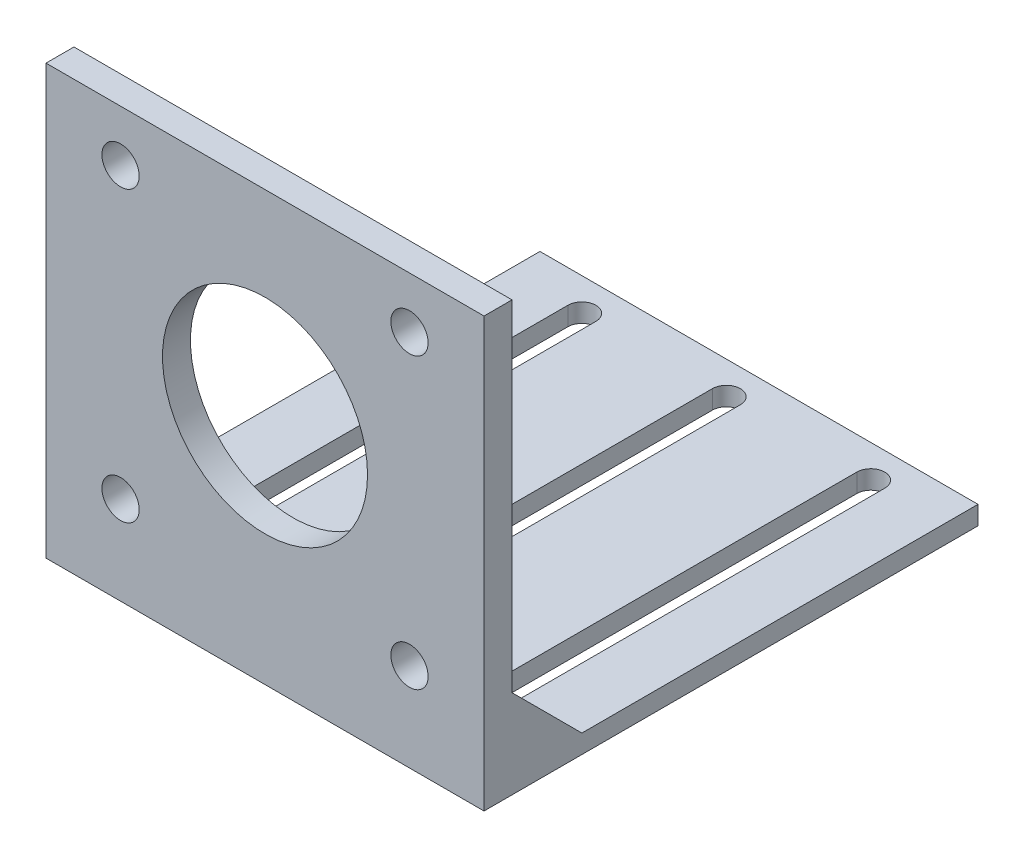
SolidWorks part; units mm, degrees
note: The reader was unsure of these and kept them because the rebuilt part matched: shared geometry of "Sketch2<3>".
ref_plane "Front Plane" through (0, 0, 0) normal (0, 0, 1) x (1, 0, 0)
ref_plane "Top Plane" through (0, 0, 0) normal (0, 1, 0) x (1, 0, 0)
ref_plane "Right Plane" through (0, 0, 0) normal (1, 0, 0) x (0, 0, -1)
sketch "Sketch2" plane through (0, 0, 0) normal (0, 0, 1) x (1, 0, 0)
  line L0 (0, 0) -> (0, 42)
  line L1 (0, 42) -> (47, 42)
  line L2 (47, 42) -> (47, 0)
  line L3 (47, 0) -> (0, 0)
  line L4 (23.5, 42) -> (23.5, -49958) construction
  line L5 (42, 21) -> (-49958, 21) construction
  line L6 (47, 0) -> (47, -4)
  line L7 (47, -4) -> (0, -4)
  line L8 (0, -4) -> (0, 0)
  circle A0 centre (23.5, 21) radius 11
  circle A1 centre (8, 5.5) radius 2
  circle A2 centre (39, 5.5) radius 2
  circle A3 centre (39, 36.5) radius 2
  circle A4 centre (8, 36.5) radius 2
  point P7 (23.5, 42)
  point P8 (23.5, 0)
  point P11 (47, 21)
  dimension "D3" = 22
  dimension "D4" = 4
  dimension "D1" = 47
  dimension "D2" = 42
  dimension "D5" = 8
  dimension "D6" = 5.5
  dimension "D7" = 4
extrude "Boss-Extrude1" add sketch "Sketch2" against normal blind 3 contours L3 L2 L1 L0 A2 A1 A0 A3 A4
extrude "Boss-Extrude2" add sketch "Sketch2<3>" against normal blind 3 contours L8 L7 L6 L3
sketch "Sketch2<3>" plane through (0, 0, 0) normal (0, 0, 1) x (1, 0, 0) same geometry as "Sketch2"
sketch "Sketch3" plane through (0, 0, -3) normal (0, 0, -1) x (-1, 0, 0)
  line L0 (-47, -4) -> (-47, -2)
  line L1 (-47, 42) -> (-47, -4) construction
  line L2 (-47, -2) -> (0, -2)
  line L3 (0, -4) -> (0, 42) construction
  line L4 (0, -2) -> (0, -4)
  line L5 (0, -4) -> (-47, -4)
  dimension "D1" = 2
extrude "Boss-Extrude3" add sketch "Sketch3" along normal blind 50
sketch "Sketch8" plane through (0, 0, 0) normal (1, 0, 0) x (0, 0, -1)
  line L0 (3, 5.5) -> (10.5, -2)
  line L1 (3, 42) -> (3, -2) construction
  line L2 (53, -2) -> (3, -2) construction
  dimension "D1" = 7.5
  dimension "D2" = 7.5
rib "Rib1" sketch "Sketch8" sketch "Sketch8" thickness 2 parameters "D1"=2
ref_plane "Plane2" through (47, 0, 0) normal (1, 0, 0) x (0, 0, -1)
sketch "Sketch10" plane through (47, 0, 0) normal (1, 0, 0) x (0, 0, -1)
  line L0 (3, 5.5) -> (10.5, -2)
rib "Rib2" sketch "Sketch10" sketch "Sketch10" thickness 2 extrusion direction parallel to sketch draft on no parameters "D1"=2
sketch "Sketch11" plane through (0, -2, 0) normal (0, 1, 0) x (1, 0, 0)
  line L0 (8, 49.5) -> (8, 10.5)
  line L3 (39, 49.5) -> (39, 10.5)
  line L4 (23.5, 49.5) -> (23.5, 10.5)
  line L5 (8, 49.5) -> (8, 10.5) construction
  line L6 (9.5, 49.5) -> (9.5, 10.5)
  line L7 (6.5, 49.5) -> (6.5, 10.5)
  line L8 (23.5, 10.5) -> (23.5, 49.5) construction
  line L9 (22, 10.5) -> (22, 49.5)
  line L10 (25, 10.5) -> (25, 49.5)
  line L11 (39, 49.5) -> (39, 10.5) construction
  line L12 (40.5, 49.5) -> (40.5, 10.5)
  line L13 (37.5, 49.5) -> (37.5, 10.5)
  line L14 (0, 53) -> (47, 53) construction
  line L15 (47, -25.3) -> (47, 25.3) construction
  line L16 (0, 53) -> (0, 10.5) construction
  arc A0 (9.5, 49.5) -> (6.5, 49.5) centre (8, 49.5) ccw
  arc A1 (6.5, 10.5) -> (9.5, 10.5) centre (8, 10.5) ccw
  arc A2 (22, 10.5) -> (25, 10.5) centre (23.5, 10.5) ccw
  arc A3 (25, 49.5) -> (22, 49.5) centre (23.5, 49.5) ccw
  arc A4 (40.5, 49.5) -> (37.5, 49.5) centre (39, 49.5) ccw
  arc A5 (37.5, 10.5) -> (40.5, 10.5) centre (39, 10.5) ccw
  point P6 (8, 30)
  point P11 (23.5, 30)
  point P16 (39, 30)
  point P23 (23.5, 53)
  point P24 (23.5, 10.5211)
  point P25 (0, 0)
  point P27 (23.5, 49.4787)
  point P28 (23.5, 51)
  point P29 (0, 0)
  point P31 (0, 0)
  point P32 (0, 0)
  point P35 (0, 0)
  point P36 (0, 0)
  point P37 (0, 0)
  dimension "D4" = 2
  dimension "D6" = 6.5
  dimension "D1" = 3
  dimension "D2" = 3
  dimension "D3" = 3
  dimension "D5" = 6.5
extrude "Cut-Extrude1" cut sketch "Sketch11" against normal blind 50 contours L9 A3 L10 A2 | L6 A1 L7 A0 | L12 A5 L13 A4
